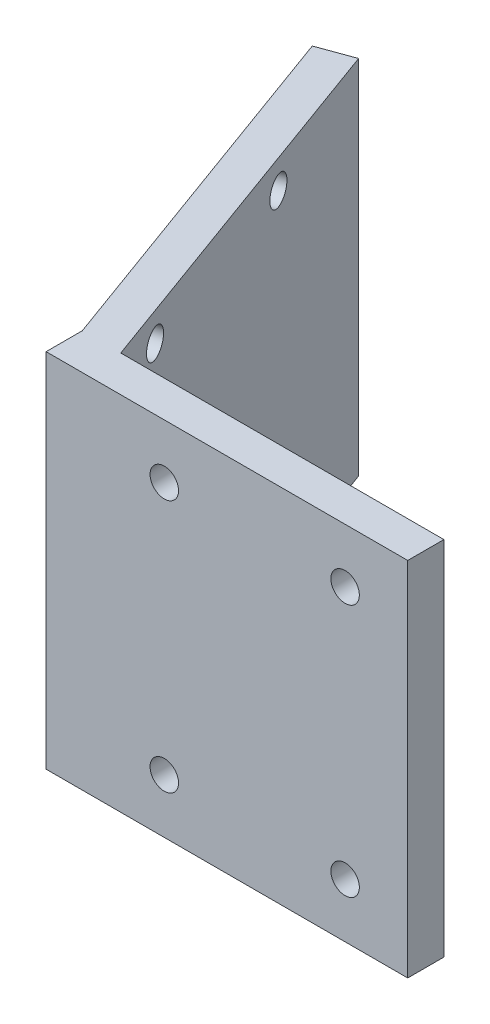
SolidWorks part; units mm, degrees
ref_plane "Front Plane" through (0, 0, 0) normal (0, 0, 1) x (1, 0, 0)
ref_plane "Top Plane" through (0, 0, 0) normal (0, 1, 0) x (1, 0, 0)
ref_plane "Right Plane" through (0, 0, 0) normal (1, 0, 0) x (0, 0, -1)
sketch "Sketch1" plane through (0, 0, 0) normal (0, 1, 0) x (1, 0, 0)
  line L0 (0, 0) -> (0, -2.54)
  line L1 (0, -2.54) -> (25.4, -2.54)
  line L2 (25.4, 0) -> (25.4, -2.54)
  line L3 (2.703, 0) -> (25.4, 0)
  line L4 (2.3868, 0.8687) -> (2.703, 0)
  line L5 (0, 0) -> (-9.2448, 25.4)
  line L6 (0, 0) -> (0, 133.517) construction
  line L7 (2.3868, 0.8687) -> (-6.858, 26.2687)
  line L8 (-9.2448, 25.4) -> (-6.858, 26.2687)
  dimension "D6" = 2.54
extrude "Boss-Extrude1" add sketch "Sketch1" along normal blind 25.4
sketch "Sketch2" plane through (0, 0, 0) normal (-0.9397, 0, 0.342) x (0.342, 0, 0.9397)
  line L0 (-27.0301, 12.7) -> (-17.6041, 12.7) construction
  line L1 (-27.0301, 25.4) -> (-27.0301, 0) construction
  line L2 (-17.6041, 12.7) -> (-17.6041, 32.6456) construction
  line L3 (-17.6041, 32.6456) -> (-17.6041, -5.1398) construction
  line L4 (-24.0208, 0) -> (-13.5151, 0) construction
  line L5 (-27.0301, 0) -> (0, 0) construction
  line L6 (-24.0208, 2) -> (-17.6041, 2)
  line L7 (-24.0208, 2) -> (-13.5151, 2) construction
  line L8 (-3.1041, 32.6456) -> (-3.1041, -5.1398)
  line L9 (-17.6041, 2) -> (-3.1041, 2) construction
  circle A0 centre (-17.6041, 2) radius 1
  circle A1 centre (-3.1041, 2) radius 1
  circle A2 centre (-3.1041, 23.4) radius 1
  circle A3 centre (-17.6041, 23.4) radius 1
  point P22 (0, 0)
  point P23 (0, 0)
  point P24 (0, 0)
  dimension "D2" = 2
  dimension "D4" = 2
  dimension "D1" = 2
  dimension "D3" = 14.5
extrude "Cut-Extrude1" cut sketch "Sketch2" against normal blind 25.4 contours A0 region at (-6.021, 1.0283, -16.5425)
extrude "Cut-Extrude2" cut sketch "Sketch2<4>" against normal blind 25.4 contours A3
sketch "Sketch2<4>" plane through (0, 0, 0) normal (-0.9397, 0, 0.342) x (0.342, 0, 0.9397) same geometry as "Sketch2"
extrude "Cut-Extrude3" cut sketch "Sketch2<5>" against normal blind 25.4 contours A1
sketch "Sketch2<5>" plane through (0, 0, 0) normal (-0.9397, 0, 0.342) x (0.342, 0, 0.9397) same geometry as "Sketch2"
extrude "Cut-Extrude4" cut sketch "Sketch2<6>" against normal blind 25.4 contours A2
sketch "Sketch2<6>" plane through (0, 0, 0) normal (-0.9397, 0, 0.342) x (0.342, 0, 0.9397) same geometry as "Sketch2"
sketch "Sketch3" plane through (0, 0, 0) normal (0, 0, -1) x (-1, 0, 0)
  line L0 (-25.4, 25.4) -> (-2.703, 25.4) construction
  line L1 (-2.703, 12.7) -> (-37.9381, 12.7) construction
  line L2 (-2.703, 25.4) -> (-2.703, 0) construction
  line L3 (-21.0015, 3.81) -> (-7.051, 3.81) construction
  circle A0 centre (-21.0015, 21.59) radius 1
  circle A1 centre (-21.0015, 3.81) radius 1
  circle A2 centre (-8.3015, 21.59) radius 1
  circle A3 centre (-8.3015, 3.81) radius 1
  dimension "D1" = 3.81
  dimension "D2" = 2
  dimension "D3" = 12.7
  dimension "D4" = 2
extrude "Cut-Extrude5" cut sketch "Sketch3" against normal blind 25.4
